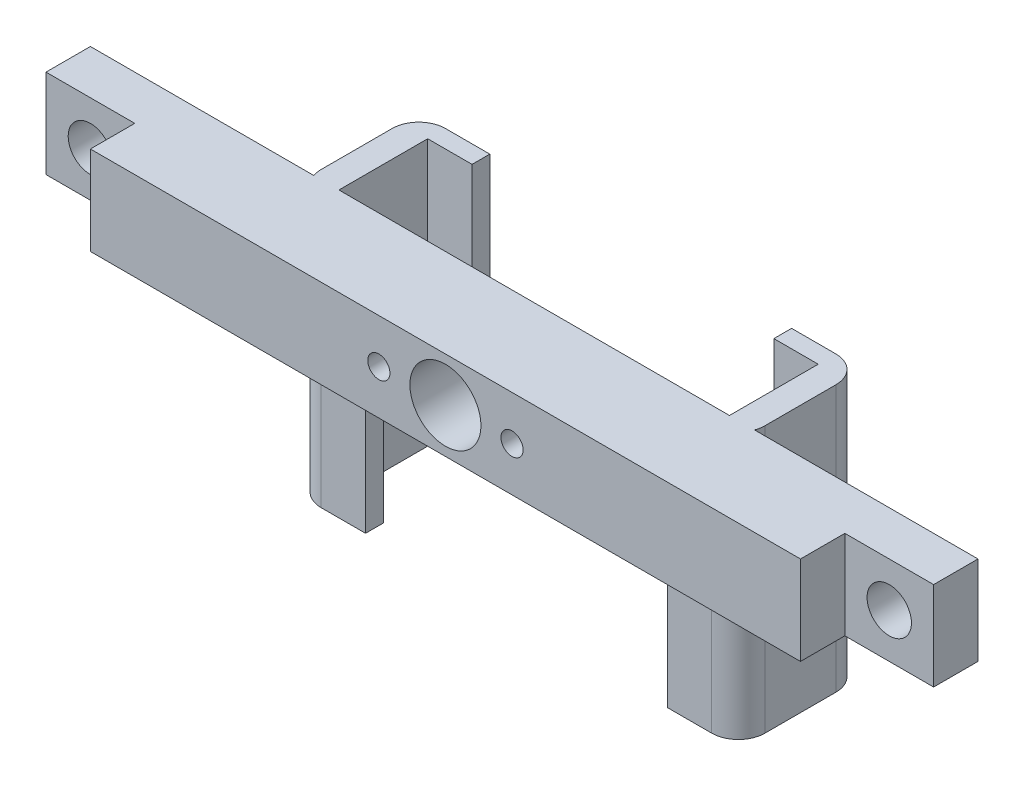
SolidWorks part; units mm, degrees
ref_plane "Front Plane" through (0, 0, 0) normal (0, 0, 1) x (1, 0, 0)
ref_plane "Top Plane" through (0, 0, 0) normal (0, 1, 0) x (1, 0, 0)
ref_plane "Right Plane" through (0, 0, 0) normal (1, 0, 0) x (0, 0, -1)
sketch "Sketch1" plane through (0, 0, 0) normal (0, 0, 1) x (1, 0, 0)
  line L1 (-50, 5) -> (50, 5)
  line L2 (-50, 5) -> (-50, -5)
  line L3 (-50, -5) -> (50, -5)
  line L4 (50, 5) -> (50, -5)
  line L5 (-50, 5) -> (50, -5) construction
  line L6 (-50, -5) -> (50, 5) construction
  point P0 (0, 0)
  dimension "D1" = 100
  dimension "D2" = 10
extrude "Boss-Extrude1" add sketch "Sketch1" along normal blind 10
sketch "Sketch2" plane through (0, 5, 0) normal (0, 1, 0) x (1, 0, 0)
  line L5 (-50, -10) -> (-40, -10)
  line L6 (-50, -10) -> (-50, -5)
  line L7 (-50, -5) -> (-40, -5)
  line L8 (-40, -10) -> (-40, -5)
  dimension "D1" = 10
  dimension "D2" = 5
sketch "Sketch6" plane through (0, 0, 0) normal (0, 0, -1) x (-1, 0, 0)
  line L0 (0, 5) -> (0, -5) construction
  line L1 (-25, 5) -> (-25, -5)
  line L3 (-25, 5) -> (-22, 5)
  line L4 (-50, 5) -> (-50, -5)
  line L5 (-50, -5) -> (50, -5)
  line L6 (-50, 5) -> (-50, -5)
  line L7 (50, 5) -> (-50, 5)
  line L9 (-50, -5) -> (50, -5)
  line L11 (50, 5) -> (-50, 5)
  line L12 (-22, 5) -> (-22, -5)
  line L13 (-22, -5) -> (-25, -5)
  line L17 (50, -5) -> (50, 5)
  line L18 (50, -5) -> (50, 5)
  line M11 (-50, -5) -> (50, -5)
  line M13 (50, 5) -> (-50, 5)
  dimension "D2" = 25
  dimension "D3" = 3
  dimension "D1" = 0
extrude "Boss-Extrude2" add sketch "Sketch6" along normal blind 12 contours L12 L1 M13 M11 region at (23.5, 0, 0)
sketch "Sketch8" plane through (22, 0, 0) normal (-1, 0, 0) x (0, 0, 1)
  line L0 (-12, -5) -> (0, -5) construction
  line L1 (-12, 5) -> (-10, 5)
  line L2 (-12, 5) -> (-12, -5)
  line L3 (-12, -5) -> (-10, -5)
  line L4 (-10, 5) -> (-10, -5)
  dimension "D1" = 2
extrude "Boss-Extrude3" add sketch "Sketch8" along normal blind 5
sketch "Sketch9" plane through (0, -5, 0) normal (0, -1, 0) x (1, 0, 0)
  line L0 (17, -12) -> (17, 0) construction
  line L1 (-50, 0) -> (22, 0) construction
  line L2 (17, 0) -> (22, 0)
  line L4 (17, 0) -> (17, 2)
  line L5 (17, 2) -> (25, 2)
  line L6 (25, 0) -> (25, 2)
  line L7 (22, 0) -> (22, -10)
  line L8 (22, -10) -> (17, -10)
  line L9 (17, -10) -> (17, -12)
  line L10 (17, -12) -> (25, -12)
  line L11 (25, -12) -> (25, 0)
  line L12 (25, 0) -> (25, 2)
  line L13 (-50, 10) -> (-50, 0) construction
  line L14 (-50, 10) -> (50, 10) construction
  line M16 (-50, 0) -> (22, 0)
  line M17 (22, 0) -> (22, -10)
  line M18 (22, -10) -> (17, -10)
  line M19 (17, -10) -> (17, -12)
  line M20 (17, -12) -> (25, -12)
  line M21 (25, -12) -> (25, 0)
  dimension "D1" = 8
  dimension "D2" = 2
  dimension "D3" = 2
extrude "Boss-Extrude4" add sketch "Sketch9" along normal blind 20 contours L6 L5 L4 M21 M16 M17 M18 M19 M20 region at (22.2097, -5, -5)
mirror "Mirror3" about plane through (0, 0, 0) normal (1, 0, 0) of "Boss-Extrude4", "Boss-Extrude3", "Boss-Extrude2"
extrude "Cut-Extrude1" cut sketch "Sketch2" against normal blind 10
mirror "Mirror4" about plane through (0, 0, 0) normal (1, 0, 0) of "Cut-Extrude1"
sketch "Sketch10" plane through (0, 0, 5) normal (0, 0, 1) x (1, 0, 0)
  line L0 (50, -5) -> (50, 5) construction
  line L1 (40, -5) -> (50, -5) construction
  circle A0 centre (45, 0) radius 2.5
  dimension "D1" = 5
  dimension "D2" = 5
  dimension "D3" = 5
extrude "Cut-Extrude2" cut sketch "Sketch10" against normal up to next
mirror "Mirror5" about plane through (0, 0, 0) normal (1, 0, 0) of "Cut-Extrude2"
sketch "Sketch12" plane through (0, 0, 0) normal (0, 0, -1) x (-1, 0, 0)
  line L0 (0, 5) -> (0, -5) construction
  line L1 (-22, 5) -> (22, 5) construction
  line L2 (17, -5) -> (-17, -5) construction
sketch "Sketch13" plane through (0, 0, 0) normal (0, 0, -1) x (-1, 0, 0)
  line L0 (0, 0) -> (-7.5, 0) construction
  line L1 (0, 0) -> (7.5, 0) construction
  circle A0 centre (0, 0) radius 4
  circle A1 centre (-7.5, 0) radius 1.25
  circle A2 centre (7.5, 0) radius 1.25
  dimension "D1" = 8
  dimension "D4" = 2.5
  dimension "D5" = 2.5
  dimension "D2" = 7.5
  dimension "D3" = 7.5
extrude "Cut-Extrude3" cut sketch "Sketch13" against normal up to next
fillet "Fillet1" radius 3 2 edges at (25, -10, -12) (-25, -10, -12)
fillet "Fillet2" radius 3 2 edges at (-25, -15, 2) (25, -15, 2)
